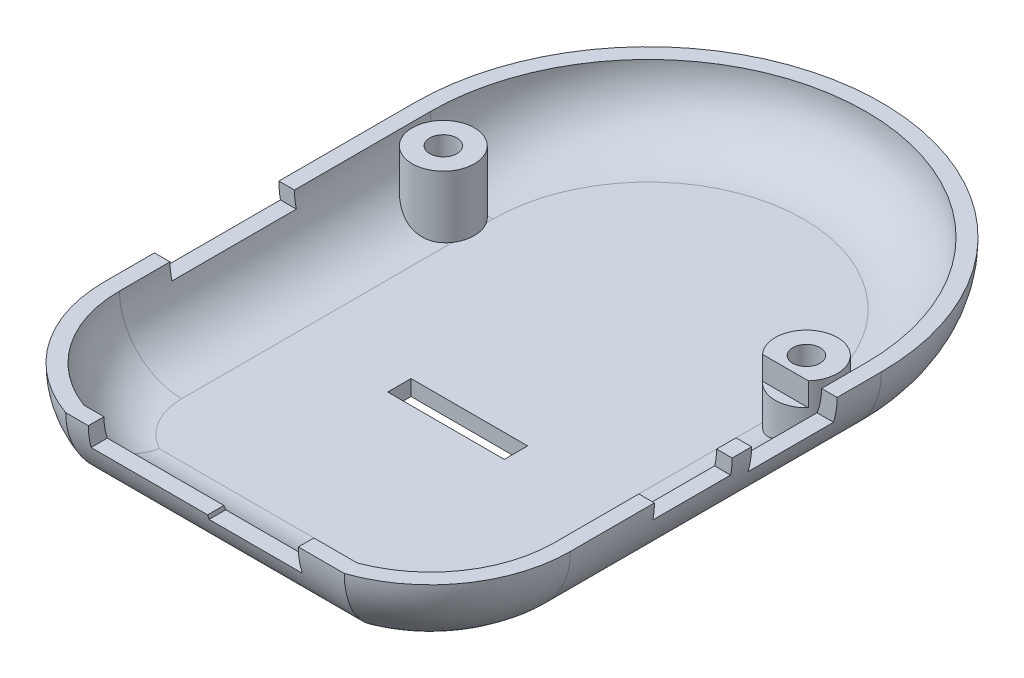
SolidWorks part; units mm, degrees
ref_plane "前视基准面" through (0, 0, 0) normal (0, 0, 1) x (1, 0, 0)
ref_plane "上视基准面" through (0, 0, 0) normal (0, 1, 0) x (1, 0, 0)
ref_plane "右视基准面" through (0, 0, 0) normal (1, 0, 0) x (0, 0, -1)
sketch "草图1" plane through (0, 0, 0) normal (0, 1, 0) x (1, 0, 0)
  line L0 (-15.6837, -23.9917) -> (61.6999, -23.9917) construction
  line L2 (-13.8877, 16.0083) -> (-13.8877, -23.9917)
  line L4 (46.1123, 16.0083) -> (46.1123, -23.9917)
  line L5 (-1.8038, -40.9917) -> (34.0283, -40.9917)
  arc A0 (46.1123, 16.0083) -> (-13.8877, 16.0083) centre (16.1123, 16.0083) ccw
  arc A3 (-13.8877, -23.9917) -> (-1.8038, -40.9917) centre (4.1123, -23.9917) ccw
  arc A4 (46.1123, -23.9917) -> (34.0283, -40.9917) centre (28.1123, -23.9917) cw
  dimension "D1" = 40
  dimension "D2" = 60
  dimension "D3" = 17
  dimension "D4" = 18
  dimension "D5" = 18
extrude "凸台-拉伸1" add sketch "草图1" along normal blind 10
fillet "圆角1" radius 10 6 edges at (-13.8877, 0, 3.9917) (16.1123, 0, -46.0083) (46.1123, 0, 3.9917) (-10.559, 0, 34.4203) (16.1123, 0, 40.9917) (42.7835, 0, 34.4203)
shell "抽壳1" thickness 2
ref_plane "基准面3" through (-13.8877, 0, 0) normal (-1, 0, 0) x (0, 0, 1)
sketch "草图2" plane through (0, 10, 0) normal (0, 1, 0) x (1, 0, 0)
  line L0 (-18.3811, 16.0083) -> (57.0962, 16.0083) construction
  line L1 (16.1123, 56.4941) -> (16.1123, -63.0618) construction
  line L2 (-11.8877, 16.0083) -> (-11.8877, -23.9917) construction
  line L3 (44.1123, -23.9917) -> (44.1123, 16.0083) construction
  circle A0 centre (-7.2377, 13.0083) radius 4
  circle A1 centre (-7.2377, 13.0083) radius 1.75
  circle A2 centre (39.4623, 13.0083) radius 1.75
  circle A3 centre (39.4623, 13.0083) radius 4
  dimension "D1" = 3
  dimension "D2" = 8
  dimension "D3" = 3.5
  dimension "D4" = 46.7
extrude "凸台-拉伸2" add sketch "草图2" against normal up to body separate body
ref_plane "基准面2" through (0, 0, 40.9917) normal (0, 0, 1) x (1, 0, 0)
ref_plane "基准面1" through (46.1123, 0, 0) normal (1, 0, 0) x (0, 0, -1)
sketch "草图3" plane through (0, 0, 40.9917) normal (0, 0, 1) x (1, 0, 0)
  line L0 (1.1123, 7.4) -> (16.1123, 7.4)
  line L1 (1.1123, 10) -> (28.1123, 10)
  line L2 (1.1123, 10) -> (1.1123, 7.4)
  line L3 (16.1123, 6.8) -> (28.1123, 6.8)
  line L4 (28.1123, 10) -> (28.1123, 6.8)
  line L5 (16.1123, 17.6537) -> (16.1123, -7.9976) construction
  line L6 (16.1123, 7.4) -> (16.1123, 6.8)
  line L7 (-1.8038, 10) -> (34.0283, 10) construction
  dimension "D1" = 3.2
  dimension "D2" = 15
  dimension "D4" = 0.6
extrude "切除-拉伸1" cut sketch "草图3" against normal blind 10
sketch "草图4" plane through (46.1123, -36.1123, 0) normal (-1, 0, 0) x (0, 1, 0)
  line L1 (43.1123, 10.3083) -> (46.1123, 10.3083)
  line L2 (43.1123, 10.3083) -> (43.1123, -0.6917)
  line L3 (43.1123, -0.6917) -> (46.1123, -0.6917)
  line L4 (46.1123, 10.3083) -> (46.1123, -0.6917)
  line L7 (46.1123, -23.9917) -> (46.1123, 16.0083) construction
  dimension "D1" = 11
  dimension "D2" = 3
extrude "切除-拉伸2" cut sketch "草图4" along normal blind 15
sketch "草图5" plane through (46.1123, 0, 0) normal (1, 0, 0) x (0, 0, -1)
  line L0 (10.3083, 10) -> (16.0083, 10) construction
  line L1 (-13.1917, 10) -> (-3.1917, 10)
  line L2 (-13.1917, 10) -> (-13.1917, 8)
  line L3 (-13.1917, 8) -> (-3.1917, 8)
  line L4 (-3.1917, 10) -> (-3.1917, 8)
  line L5 (16.0083, 0) -> (16.0083, 10) construction
  dimension "D1" = 19.2
  dimension "D2" = 10
  dimension "D3" = 2
extrude "切除-拉伸3" cut sketch "草图5" against normal up to next
sketch "草图6" plane through (-13.8877, 0, 0) normal (-1, 0, 0) x (0, 0, 1)
  line L0 (-16.0083, 10) -> (23.9917, 10) construction
  line L1 (1.4917, 10) -> (17.4917, 10)
  line L2 (1.4917, 10) -> (1.4917, 8)
  line L3 (1.4917, 8) -> (17.4917, 8)
  line L4 (17.4917, 10) -> (17.4917, 8)
  line L5 (-16.0083, 10) -> (-16.0083, 0) construction
  dimension "D1" = 17.5
  dimension "D2" = 16
  dimension "D3" = 2
extrude "切除-拉伸4" cut sketch "草图6" against normal blind 10
sketch "草图7" plane through (0, 0, 0) normal (0, -1, 0) x (1, 0, 0)
  line L0 (-13.8877, -16.0727) -> (48.0606, -16.0727) construction
  line L1 (16.1123, 56.4941) -> (16.1123, -63.0618) construction
  line L4 (-13.8877, 5.5) -> (-13.8877, -5.5) construction
  circle A1 centre (-7.2377, -13.0727) radius 2.5
  circle A2 centre (39.4623, -13.0727) radius 2.5
  dimension "D1" = 3
  dimension "D3" = 5
  dimension "D4" = 46.7
extrude "切除-拉伸5" cut sketch "草图7" against normal blind 4
sketch "草图8" plane through (0, 2, 0) normal (0, 1, 0) x (1, 0, 0)
  line L0 (16.1123, 47.3367) -> (16.1123, -47.1915) construction
  line L1 (8.6123, -6.9917) -> (23.6123, -6.9917)
  line L2 (8.6123, -6.9917) -> (8.6123, -9.9917)
  line L3 (8.6123, -9.9917) -> (23.6123, -9.9917)
  line L4 (23.6123, -6.9917) -> (23.6123, -9.9917)
  line L5 (-3.8877, -23.9917) -> (-3.8877, 16.0083) construction
  line L6 (36.1123, 16.0083) -> (36.1123, -23.9917) construction
  circle A0 centre (-7.2377, 13.0083) radius 1.75 construction
  dimension "D1" = 15
  dimension "D2" = 3
  dimension "D3" = 20
extrude "切除-拉伸6" cut sketch "草图8" against normal blind 10
